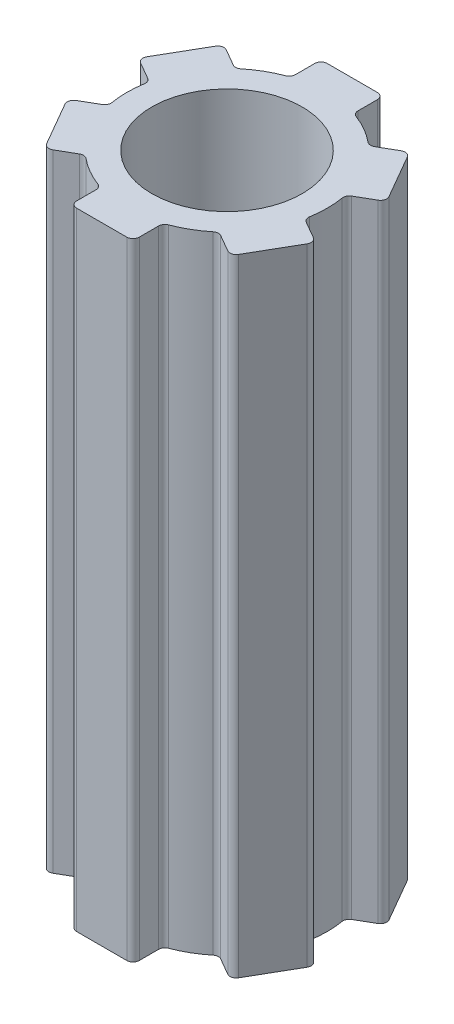
SolidWorks part; units mm, degrees
ref_plane "Front Plane" through (0, 0, 0) normal (0, 0, 1) x (1, 0, 0)
ref_plane "Top Plane" through (0, 0, 0) normal (0, 1, 0) x (1, 0, 0)
ref_plane "Right Plane" through (0, 0, 0) normal (1, 0, 0) x (0, 0, -1)
sketch "Sketch4" plane through (0, 0, 0) normal (0, 1, 0) x (1, 0, 0)
  line L0 (0, -1010.4938) -> (0, -5.08) construction
  line L1 (1.27, 5.08) -> (-1.27, 5.08)
  line L2 (-1.27, 5.08) -> (-1.27, 3.8605)
  line L3 (1.27, 5.08) -> (1.27, 3.8605)
  line L4 (3.7644, 3.6399) -> (2.7083, 3.0301)
  line L5 (5.0344, 1.4401) -> (3.7644, 3.6399)
  line L6 (5.0344, 1.4401) -> (3.9783, 0.8304)
  line L7 (5.0344, -1.4401) -> (3.9783, -0.8304)
  line L8 (3.7644, -3.6399) -> (5.0344, -1.4401)
  line L9 (3.7644, -3.6399) -> (2.7083, -3.0301)
  line L10 (1.27, -5.08) -> (1.27, -3.8605)
  line L11 (-1.27, -5.08) -> (1.27, -5.08)
  line L12 (-1.27, -5.08) -> (-1.27, -3.8605)
  line L13 (-3.7644, -3.6399) -> (-2.7083, -3.0301)
  line L14 (-5.0344, -1.4401) -> (-3.7644, -3.6399)
  line L15 (-5.0344, -1.4401) -> (-3.9783, -0.8304)
  line L16 (-5.0344, 1.4401) -> (-3.9783, 0.8304)
  line L17 (-3.7644, 3.6399) -> (-5.0344, 1.4401)
  line L18 (-3.7644, 3.6399) -> (-2.7083, 3.0301)
  line L19 (0, -4.064) -> (0, 8.2239) construction
  arc A0 (-3.9783, 0.8304) -> (-3.9783, -0.8304) centre (0, 0) ccw
  arc A1 (-1.27, 3.8605) -> (-2.7083, 3.0301) centre (0, 0) ccw
  arc A2 (2.7083, 3.0301) -> (1.27, 3.8605) centre (0, 0) ccw
  arc A3 (3.9783, -0.8304) -> (3.9783, 0.8304) centre (0, 0) ccw
  arc A4 (1.27, -3.8605) -> (2.7083, -3.0301) centre (0, 0) ccw
  arc A5 (-2.7083, -3.0301) -> (-1.27, -3.8605) centre (0, 0) ccw
  point P10 (0, 5.08)
  point P34 (0, 0)
  dimension "D3" = 8.128
  dimension "D1" = 1.27
  dimension "D2" = 5.08
  dimension "D4" = 6
extrude "Boss-Extrude2" add sketch "Sketch4" along normal blind 25.4
sketch "Sketch5" plane through (0, 25.4, 0) normal (0, 1, 0) x (1, 0, 0)
  circle A0 centre (0, 0) radius 3.048
  dimension "D1" = 6.096
extrude "Cut-Extrude1" cut sketch "Sketch5" against normal through all
ref_axis "Axis1" through (0, 0, 0) along (0, 1, 0)
fillet "Fillet1" radius 0.254 24 edges at (5.0344, 12.7, -1.4401) (3.9783, 12.7, -0.8304) (3.9783, 12.7, 0.8304) (5.0344, 12.7, 1.4401) (3.7644, 12.7, 3.6399) (2.7083, 12.7, 3.0301) (1.27, 12.7, 5.08) (1.27, 12.7, 3.8605) (-1.27, 12.7, 5.08) (-1.27, 12.7, 3.8605) (-2.7083, 12.7, 3.0301) (-3.7644, 12.7, 3.6399) (-5.0344, 12.7, 1.4401) (-3.9783, 12.7, 0.8304) (-3.9783, 12.7, -0.8304) (-5.0344, 12.7, -1.4401) (-3.7644, 12.7, -3.6399) (-1.27, 12.7, -3.8605) (-2.7083, 12.7, -3.0301) (-1.27, 12.7, -5.08) (1.27, 12.7, -5.08) (1.27, 12.7, -3.8605) (3.7644, 12.7, -3.6399) (2.7083, 12.7, -3.0301)
